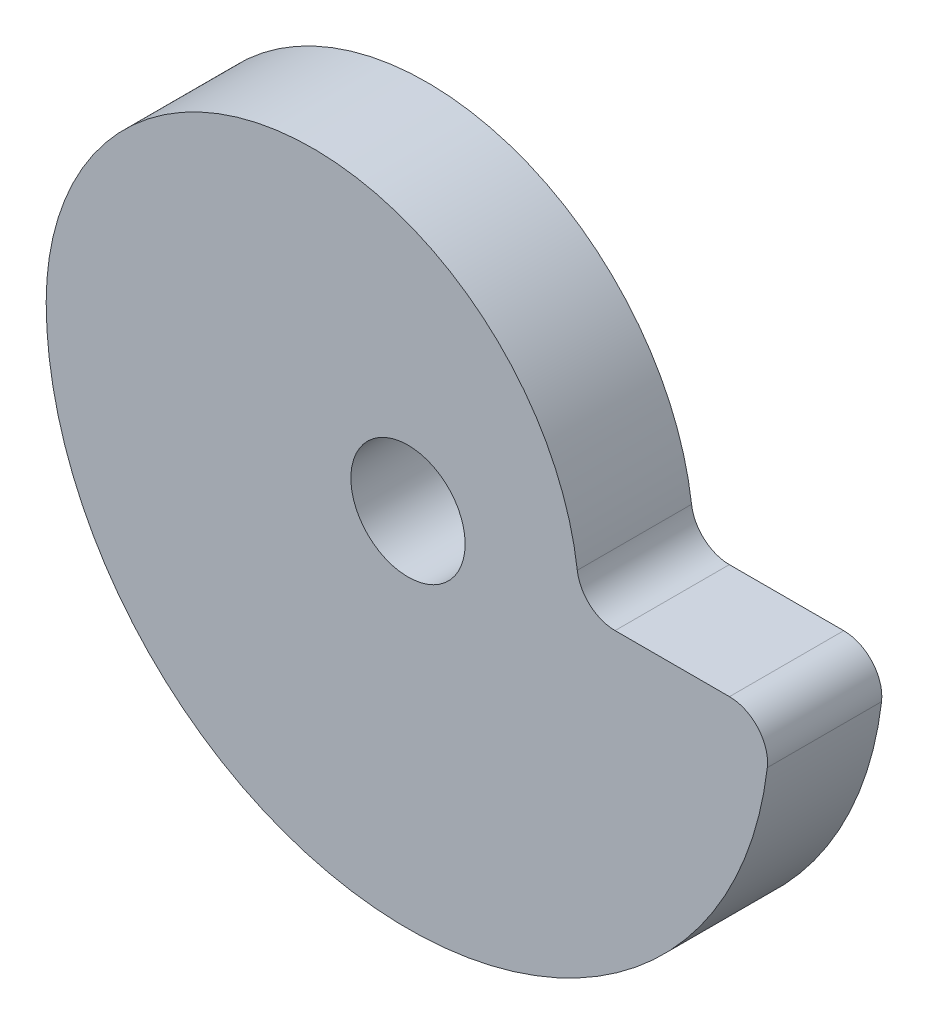
SolidWorks part; units mm, degrees
ref_plane "Front Plane" through (0, 0, 0) normal (0, 0, 1) x (1, 0, 0)
ref_plane "Top Plane" through (0, 0, 0) normal (0, 1, 0) x (1, 0, 0)
ref_plane "Right Plane" through (0, 0, 0) normal (1, 0, 0) x (0, 0, -1)
sketch "Sketch1" plane through (0, 0, 0) normal (0, 0, 1) x (1, 0, 0)
  line L0 (10.8745, 0) -> (16.8819, 0)
  circle A0 centre (0, 0) radius 3
  arc A2 (-19, 0) -> (18.8681, -2.2353) centre (0, 0) ccw
  arc A3 (8.8902, 1.75) -> (-19, 0) centre (-5, 0) ccw
  arc A4 (16.8819, 0) -> (18.8681, -2.2353) centre (16.8819, -2) cw
  arc A5 (10.8745, 0) -> (8.8902, 1.75) centre (10.8745, 2) cw
  point P10 (0, 0)
  point P11 (0, 0)
  dimension "D1" = 19
  dimension "D2" = 14
  dimension "D3" = 6
  dimension "D4" = 0
  dimension "D5" = 2
extrude "Boss-Extrude1" add sketch "Sketch1" along normal mid plane 6
